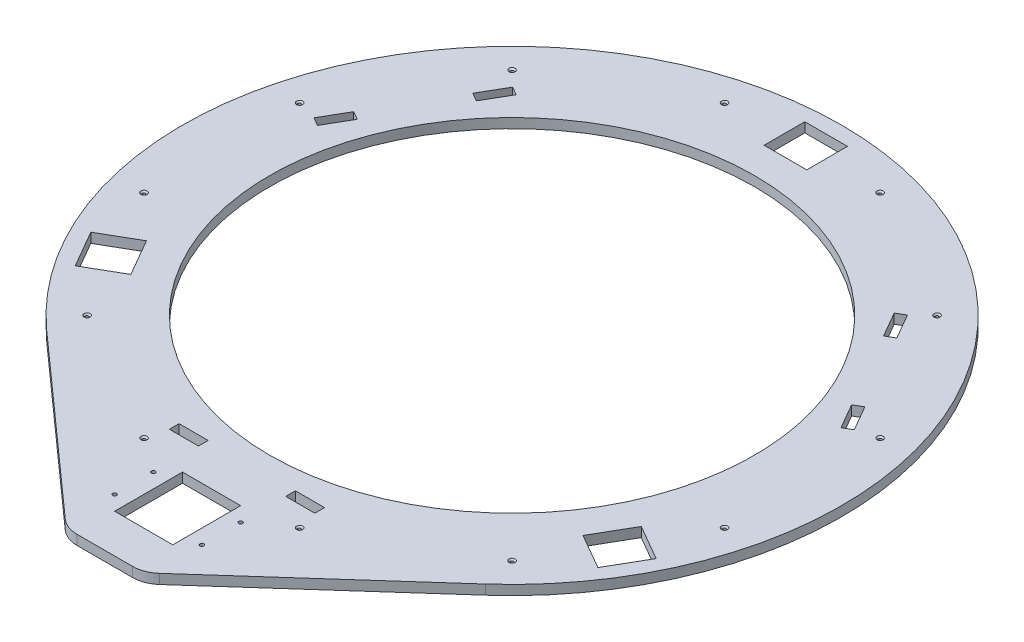
SolidWorks part; units mm, degrees
ref_plane "Front Plane" through (0, 0, 0) normal (0, 0, 1) x (1, 0, 0)
ref_plane "Top Plane" through (0, 0, 0) normal (0, 1, 0) x (1, 0, 0)
ref_plane "Right Plane" through (0, 0, 0) normal (1, 0, 0) x (0, 0, -1)
sketch "Sketch1" plane through (0, 82.4648, 0) normal (0, 1, 0) x (1, 0, 0)
  circle A6 centre (0, 0) radius 340
  circle A12 centre (0, 0) radius 340
  circle A20 centre (0, 0) radius 250
  dimension "D3" = 500
  dimension "D1" = 680
extrude "Boss-Extrude1" add sketch "Sketch1" against normal blind 10 contours A6 A20 region at (-330.3833, 82.4648, 0)
sketch "Sketch7" plane through (0, 72.4648, 0) normal (0, -1, 0) x (1, 0, 0)
  line L0 (75, 278.5) -> (45, 278.5)
  line L1 (75, 268.5) -> (75, 278.5)
  line L2 (45, 268.5) -> (75, 268.5)
  line L3 (45, 278.5) -> (45, 268.5)
  line L4 (-45, 278.5) -> (-45, 268.5)
  line L5 (-45, 268.5) -> (-75, 268.5)
  line L6 (-75, 268.5) -> (-75, 278.5)
  line L7 (-75, 278.5) -> (-45, 278.5)
  line L8 (0, 0) -> (0, 291) construction
  line L9 (-45, 268.5) -> (45, 268.5) construction
  line L10 (-45, 278.5) -> (45, 278.5) construction
  circle A0 centre (0, 0) radius 291 construction
  dimension "D4" = 582
  dimension "D1" = 90
  dimension "D2" = 10
  dimension "D3" = 30
  dimension "D5" = 12.5
extrude "Cut-Extrude2" cut sketch "Sketch7" against normal blind 10
pattern_circular "CirPattern3" count 3 over 360 about axis through (0, 72.4648, 0) along (0, 1, 0) of "Cut-Extrude2"
sketch "Sketch8" plane through (0, 82.4648, 0) normal (0, 1, 0) x (1, 0, 0)
  line L0 (0, 0) -> (0, -420) construction
  line L1 (-40, -420) -> (40, -420)
  line L2 (40, -420) -> (226.3788, -253.6782)
  line L3 (-40, -420) -> (-226.3788, -253.6782)
  circle A1 centre (0, 0) radius 340 construction
  arc A2 (226.3788, -253.6782) -> (-226.3788, -253.6782) centre (0, 0) cw
  dimension "D2" = 80
  dimension "D1" = 420
extrude "Boss-Extrude3" add sketch "Sketch8" against normal blind 10
sketch "Sketch9" plane through (0, 82.4648, 0) normal (0, 1, 0) x (1, 0, 0)
  line L0 (0, 0) -> (0, -380) construction
  line L1 (-30, -380) -> (-30, -310)
  line L2 (-30, -380) -> (30, -380)
  line L4 (-30, -310) -> (30, -310)
  line L5 (30, -380) -> (30, -310)
  dimension "D1" = 60
  dimension "D2" = 70
  dimension "D3" = 310
extrude "Cut-Extrude3" cut sketch "Sketch9" against normal blind 10
sketch "Sketch10" plane through (0, 82.4648, 0) normal (0, 1, 0) x (1, 0, 0)
  line L0 (0, 0) -> (489.6536, -282.7016) construction
  line L1 (0, 0) -> (0, 475.2363) construction
  line L2 (233.2192, -160.0526) -> (255.2192, -121.9474)
  line L5 (255.2192, -121.9474) -> (291.5922, -142.9474)
  line L6 (291.5922, -142.9474) -> (269.5922, -181.0526)
  line L8 (233.2192, -160.0526) -> (269.5922, -181.0526)
  point P14 (255.641, -147.5944)
  point P15 (244.2192, -141)
  dimension "D1" = 120
  dimension "D2" = 282
  dimension "D3" = 44
  dimension "D4" = 42
extrude "Cut-Extrude4" cut sketch "Sketch10" against normal blind 10
pattern_circular "CirPattern4" count 3 over 360 about axis through (0, 82.4648, 0) along (0, 1, 0) of "Cut-Extrude4"
sketch "Sketch11" plane through (0, 82.4648, 0) normal (0, 1, 0) x (1, 0, 0)
  circle A0 centre (-45, -365) radius 2
  circle A1 centre (-45, -325) radius 2
  circle A2 centre (45, -365) radius 2
  circle A3 centre (45, -325) radius 2
  dimension "D1" = 4
extrude "Cut-Extrude5" cut sketch "Sketch11" against normal blind 10
fillet "Fillet1" radius 30 2 edges at (40, 77.4648, 420) (-40, 77.4648, 420)
hole_wizard "CSK for M3 Flat Head Machine Screw1" positions "Sketch12" profile "Sketch13" countersink size "M3" standard "ANSI Metric" end condition through all
sketch "Sketch12" plane through (0, 82.4648, 0) normal (0, 1, 0) x (1, 0, 0)
  line L0 (80.2339, 299.437) -> (0, 0) construction
  line L2 (0, 0) -> (0, 423.7069) construction
  circle A0 centre (0, 0) radius 310 construction
  point P0 (80.2339, 299.437)
  point P21 (219.2031, 219.2031)
  point P22 (299.437, 80.2339)
  point P23 (299.437, -80.2339)
  point P24 (219.2031, -219.2031)
  point P25 (80.2339, -299.437)
  point P26 (-80.2339, -299.437)
  point P27 (-219.2031, -219.2031)
  point P28 (-299.437, -80.2339)
  point P29 (-299.437, 80.2339)
  point P30 (-219.2031, 219.2031)
  point P31 (-80.2339, 299.437)
  point P32 (0, 0)
sketch "Sketch13" plane through (80.2339, 82.4648, -299.437) normal (1, 0, 0) x (0, 0, 1)
  line L0 (0, 0) -> (0, 10)
  line L1 (0, 10) -> (1.7, 10)
  line L2 (1.7, 10) -> (1.7, 1.45)
  line L3 (1.7, 1.45) -> (3.15, 0)
  line L4 (3.15, 0) -> (0, 0)
  line L5 (-1.7, 1.45) -> (-3.15, 0) construction
  line L6 (0, -6.35) -> (0, 107.95) construction
  dimension "Thru Hole Dia." = 3.4
  dimension "Thru Hole Depth" = 10
  dimension "Near C'Sink Dia." = 6.3
  dimension "Near C'Sink Angle" = 90
